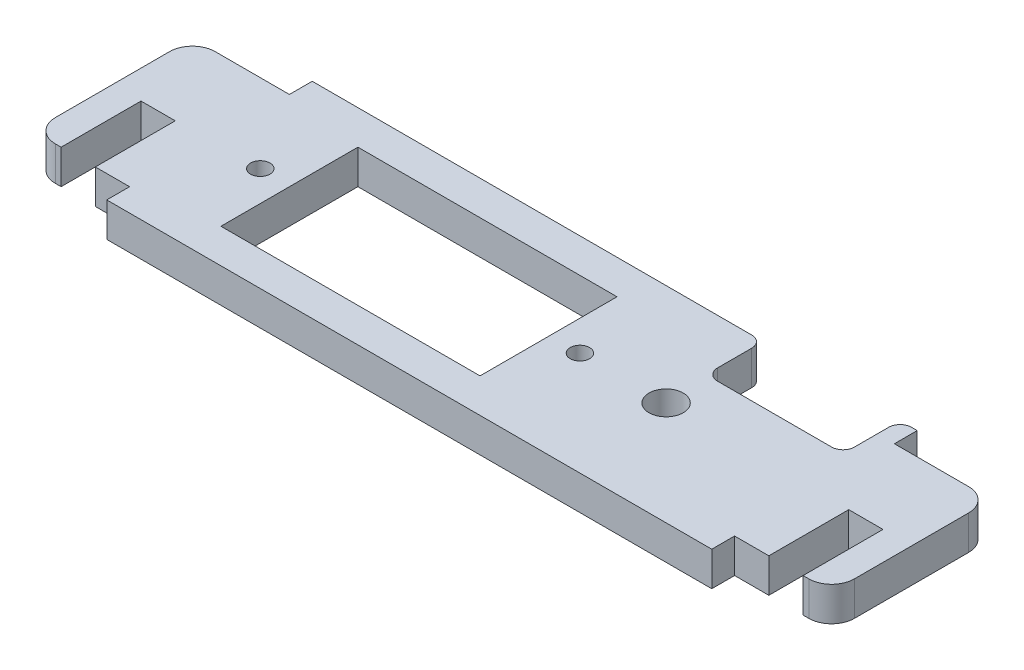
SolidWorks part; units mm, degrees
ref_plane "Front Plane" through (0, 0, 0) normal (0, 0, 1) x (1, 0, 0)
ref_plane "Top Plane" through (0, 0, 0) normal (0, 1, 0) x (1, 0, 0)
ref_plane "Right Plane" through (0, 0, 0) normal (1, 0, 0) x (0, 0, -1)
sketch "Sketch1" plane through (0, 0, 0) normal (0, 1, 0) x (1, 0, 0)
  line L5 (-9.8206, 11.01) -> (-9.8206, 1.01)
  line L7 (-79.8206, 1.01) -> (-79.8206, 11.01)
  line L15 (-77.8206, 13.01) -> (-71.3206, 13.01)
  line L17 (-77.8206, -0.99) -> (-71.3206, -0.99)
  line L21 (-71.3206, -0.99) -> (-71.3206, -2.99)
  line L22 (-71.3206, 13.01) -> (-71.3206, 15.01)
  line L24 (-71.3206, 15.01) -> (-32.8206, 15.01)
  line L26 (-18.3206, 13.01) -> (-11.8206, 13.01)
  line L27 (-11.8206, -0.99) -> (-18.3206, -0.99)
  line L28 (-18.3206, -0.99) -> (-18.3206, -2.99)
  line L29 (-18.3206, -2.99) -> (-71.3206, -2.99)
  line L30 (-18.3206, 13.01) -> (-18.3206, 15.01)
  line L31 (-18.3206, 15.01) -> (-18.8206, 15.01)
  line L32 (-19.8206, 14.01) -> (-19.8206, 11.01)
  line L33 (-20.8206, 10.01) -> (-30.8206, 10.01)
  line L34 (-31.8206, 11.01) -> (-31.8206, 14.01)
  arc A0 (-79.8206, 11.01) -> (-77.8206, 13.01) centre (-77.8206, 11.01) cw
  arc A1 (-11.8206, 13.01) -> (-9.8206, 11.01) centre (-11.8206, 11.01) cw
  arc A2 (-9.8206, 1.01) -> (-11.8206, -0.99) centre (-11.8206, 1.01) cw
  arc A3 (-77.8206, -0.99) -> (-79.8206, 1.01) centre (-77.8206, 1.01) cw
  arc A5 (-18.8206, 15.01) -> (-19.8206, 14.01) centre (-18.8206, 14.01) ccw
  arc A7 (-19.8206, 11.01) -> (-20.8206, 10.01) centre (-20.8206, 11.01) cw
  arc A8 (-30.8206, 10.01) -> (-31.8206, 11.01) centre (-30.8206, 11.01) cw
  arc A9 (-31.8206, 14.01) -> (-32.8206, 15.01) centre (-32.8206, 14.01) ccw
  dimension "D1" = 2
  dimension "D2" = 2
  dimension "D3" = 2
  dimension "D4" = 2
  dimension "D6" = 14
  dimension "D8" = 8.5
  dimension "D9" = 2
  dimension "D11" = 1
  dimension "D12" = 1
  dimension "D14" = 1
  dimension "D10" = 1
  dimension "D5" = 70
  dimension "D13" = 5
  dimension "D15" = 12
  dimension "D16" = 53
  dimension "D17" = 0.5
extrude "Boss-Extrude1" add sketch "Sketch1" along normal blind 3
sketch "Sketch2" plane through (0, 3, 0) normal (0, 1, 0) x (1, 0, 0)
  line L1 (-64.3206, 12.01) -> (-41.6206, 12.01)
  line L2 (-64.3206, 12.01) -> (-64.3206, 0.01)
  line L3 (-64.3206, 0.01) -> (-41.6206, 0.01)
  line L4 (-41.6206, 12.01) -> (-41.6206, 0.01)
  line L7 (-32.8206, 15.01) -> (-71.3206, 15.01) construction
  line L8 (-71.3206, -0.99) -> (-71.3206, -2.99) construction
  dimension "D1" = 12
  dimension "D2" = 22.7
  dimension "D3" = 3
  dimension "D4" = 7
extrude "Cut-Extrude1" cut sketch "Sketch2" against normal blind 3
sketch "Sketch3" plane through (0, 3, 0) normal (0, 1, 0) x (1, 0, 0)
  line L0 (-18.3206, -0.99) -> (-11.8206, -0.99) construction
  line L1 (-15.3206, -0.99) -> (-12.3206, -0.99)
  line L2 (-15.3206, -0.99) -> (-15.3206, 6.01)
  line L3 (-15.3206, 6.01) -> (-12.3206, 6.01)
  line L4 (-12.3206, -0.99) -> (-12.3206, 6.01)
  line L5 (-18.3206, -2.99) -> (-18.3206, -0.99) construction
  line L6 (-11.8206, 13.01) -> (-18.3206, 13.01) construction
  line L7 (-77.8206, -0.99) -> (-71.3206, -0.99) construction
  line L8 (-74.3206, -0.99) -> (-77.3206, -0.99)
  line L9 (-74.3206, -0.99) -> (-74.3206, 6.01)
  line L10 (-74.3206, 6.01) -> (-77.3206, 6.01)
  line L11 (-77.3206, -0.99) -> (-77.3206, 6.01)
  line L12 (-71.3206, -0.99) -> (-71.3206, -2.99) construction
  dimension "D1" = 3
  dimension "D2" = 3
  dimension "D3" = 7
  dimension "D4" = 3
  dimension "D5" = 3
extrude "Cut-Extrude2" cut sketch "Sketch3" against normal blind 3
sketch "Sketch4" plane through (0, 3, 0) normal (0, 1, 0) x (1, 0, 0)
  line L1 (-9.8206, 1.01) -> (-9.8206, 11.01) construction
  line L2 (-32.8206, 15.01) -> (-71.3206, 15.01) construction
  circle A0 centre (-31.4206, 6.11) radius 1.5
  dimension "D1" = 3
  dimension "D2" = 8.9
  dimension "D3" = 21.6
extrude "Cut-Extrude3" cut sketch "Sketch4" against normal blind 3
sketch "Sketch5" plane through (0, 3, 0) normal (0, 1, 0) x (1, 0, 0)
  line L0 (-32.8206, 15.01) -> (-71.3206, 15.01) construction
  line L1 (-41.6206, 0.01) -> (-41.6206, 12.01) construction
  line L2 (-64.3206, 12.01) -> (-64.3206, 0.01) construction
  circle A0 centre (-38.9706, 6.11) radius 0.85
  circle A1 centre (-66.9706, 6.11) radius 0.85
  dimension "D1" = 8.9
  dimension "D2" = 1.7
  dimension "D4" = 1.7
  dimension "D5" = 2.65
  dimension "D6" = 8.9
  dimension "D3" = 2.65
extrude "Cut-Extrude4" cut sketch "Sketch5" against normal blind 3
